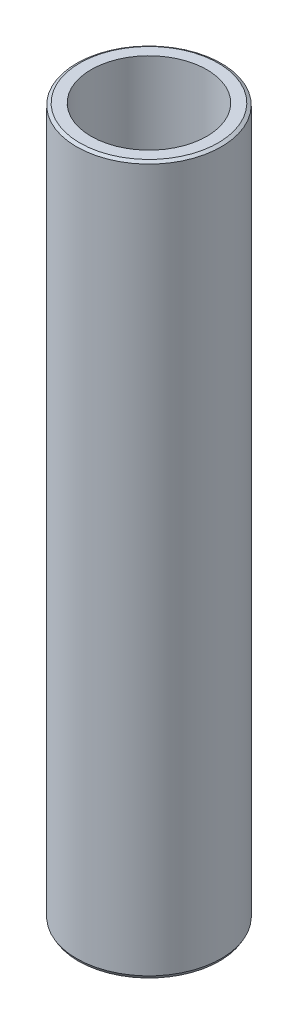
SolidWorks part; units mm, degrees
ref_plane "Front Plane" through (0, 0, 0) normal (0, 0, 1) x (1, 0, 0)
ref_plane "Top Plane" through (0, 0, 0) normal (0, 1, 0) x (1, 0, 0)
ref_plane "Right Plane" through (0, 0, 0) normal (1, 0, 0) x (0, 0, -1)
sketch "Sketch1" plane through (0, 0, 0) normal (0, 1, 0) x (1, 0, 0)
  circle A0 centre (0, 0) radius 52.5
  dimension "SHAFT_OD" = 105
extrude "Boss-Extrude1" add sketch "Sketch1" along normal blind 513.7734
sketch "Sketch2" plane through (0, 0, 0) normal (0, 1, 0) x (1, 0, 0)
  circle A0 centre (0, 0) radius 41.9792
  dimension "BORE_D" = 83.9584
extrude "Cut-Extrude1" cut sketch "Sketch2" along normal through all
chamfer "Chamfer1" distance 1.3153 angle 60 2 edges at (0, 513.7734, 52.5) (0, 0, 52.5) first distance on face at (0, 513.7734, 52.5) first distance on face at (0, 0, 41.9792)
